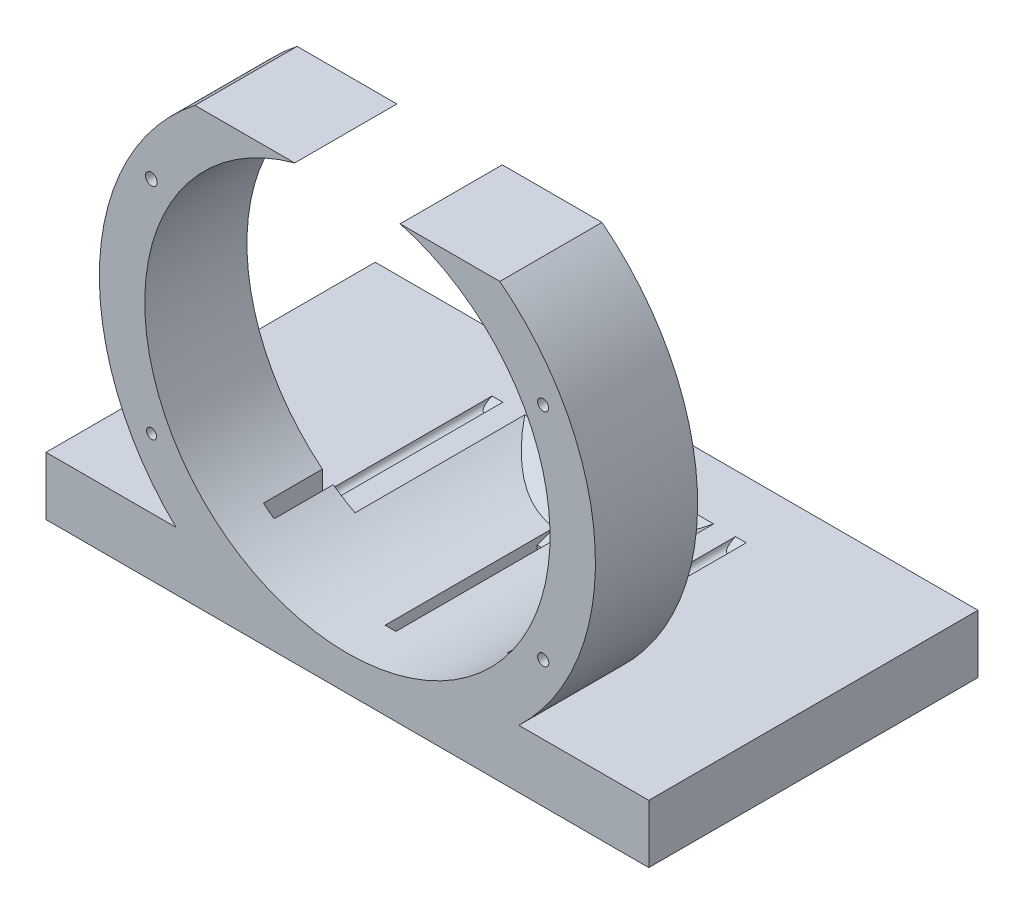
SolidWorks part; units mm, degrees
ref_plane "Front Plane" through (0, 0, 0) normal (0, 0, 1) x (1, 0, 0)
ref_plane "Top Plane" through (0, 0, 0) normal (0, 1, 0) x (1, 0, 0)
ref_plane "Right Plane" through (0, 0, 0) normal (1, 0, 0) x (0, 0, -1)
sketch "Sketch1" plane through (0, 0, 0) normal (0, 0, 1) x (1, 0, 0)
  line L0 (-34.1117, 43.7782) -> (34.1117, 43.7782)
  line L4 (28.448, -40.0843) -> (28.448, -35.2709)
  line L5 (-67.4363, -40.1112) -> (-38.3566, -40.1112)
  line L6 (-67.4363, -40.1112) -> (-67.4363, -53.1541)
  line L7 (-67.4363, -53.1541) -> (67.4363, -53.1541)
  line L8 (67.4363, -40.1112) -> (67.4363, -53.1541)
  line L9 (1.2065, -45.2975) -> (1.2065, -49.1871)
  line L10 (-1.2065, -45.2975) -> (-1.2065, -49.1871)
  line L12 (-28.448, -35.2709) -> (-28.448, -40.0843)
  line L13 (38.3566, -40.1112) -> (67.4363, -40.1112)
  line L14 (26.035, -37.0877) -> (26.035, -40.0843)
  line L16 (-26.035, -40.0843) -> (-26.035, -37.0877)
  arc A1 (-26.035, -37.1188) -> (-1.2065, -45.3229) centre (0, 0) ccw
  arc A2 (-34.1117, 43.7782) -> (-38.3566, -40.1112) centre (0, 0) ccw
  circle A3 centre (-43.8732, 24.6314) radius 1.3123
  arc A4 (38.3566, -40.1112) -> (34.1117, 43.7782) centre (0, 0) ccw
  circle A5 centre (-43.815, -24.6768) radius 1.1199
  circle A6 centre (43.815, -24.6768) radius 1.2511
  circle A7 centre (43.7914, 24.6952) radius 1.2263
  arc A9 (-1.2065, -49.1871) -> (1.2065, -49.1871) centre (0, -49.1871) ccw
  arc A10 (-28.448, -40.0843) -> (-26.035, -40.0843) centre (-27.2415, -40.0843) ccw
  arc A11 (1.2065, -45.3229) -> (26.035, -37.1188) centre (0, 0) ccw
  arc A12 (26.035, -40.0843) -> (28.448, -40.0843) centre (27.2415, -40.0843) ccw
  arc A13 (28.448, -35.3035) -> (-28.448, -35.3035) centre (0, 0) ccw
  point P8 (0, -45.339)
  dimension "D1" = 90.678
  dimension "D2" = 10.16
  dimension "D3" = 2.413
extrude "Boss-Extrude1" add sketch "Sketch1" along normal blind 22.86 contours L13 A4 L0 A1 A2 L5 L6 L7 L8 region at (-22.9528, 42.1173, 0)
sketch "Sketch2" plane through (0, 0, 0) normal (0, 0, -1) x (-1, 0, 0)
  line L0 (21.1356, -40.1112) -> (26.0353, -40.1112)
  line L1 (-67.4363, -53.1541) -> (67.4363, -53.1541)
  line L2 (-67.4363, -53.1541) -> (-67.4363, -40.1112)
  line L3 (-67.4363, -40.1112) -> (-28.4477, -40.1112)
  line L4 (67.4363, -53.1541) -> (67.4363, -40.1112)
  line L5 (1.2065, -49.1871) -> (1.2065, -45.3229)
  line L6 (28.4477, -40.1112) -> (67.4363, -40.1112)
  line L7 (-1.2065, -45.3229) -> (-1.2065, -49.1871)
  line L8 (-26.0353, -40.1112) -> (-21.1356, -40.1112)
  arc A0 (-21.1356, -40.1112) -> (-1.2065, -45.3229) centre (0, 0) ccw
  arc A1 (-28.4477, -40.1112) -> (-26.0353, -40.1112) centre (-27.2415, -40.0843) ccw
  arc A2 (-1.2065, -49.1871) -> (1.2065, -49.1871) centre (0, -49.1871) ccw
  arc A3 (26.0353, -40.1112) -> (28.4477, -40.1112) centre (27.2415, -40.0843) ccw
  arc A4 (1.2065, -45.3229) -> (21.1356, -40.1112) centre (0, 0) ccw
extrude "Boss-Extrude2" add sketch "Sketch2" along normal blind 50.8 contours L2 L3 A1 L8 A0 L7 A2 L5 A4 L0 A3 L6 L4 L1
sketch "Sketch3" plane through (0, 0, 0) normal (0, 0, -1) x (-1, 0, 0)
  line L0 (-28.448, 40.2554) -> (-28.448, 35.2709)
  line L1 (-28.448, 35.2709) -> (-26.035, 37.0877)
  line L2 (-26.035, 37.0877) -> (-26.035, 40.2554)
  line L3 (28.448, 40.2554) -> (28.448, 35.3035)
  line L4 (28.448, 35.3035) -> (26.0792, 37.0877)
  line L5 (26.0792, 37.0877) -> (26.035, 40.2554)
  arc A0 (-26.035, 40.2554) -> (-28.448, 40.2554) centre (-27.2415, 40.2554) ccw
  arc A1 (28.448, 40.2554) -> (26.0355, 40.2217) centre (27.2415, 40.2554) ccw
  arc A2 (28.448, -35.3035) -> (11.7939, 43.7782) centre (0, 0) ccw construction
  arc M5 (11.7939, 43.7782) -> (28.448, -35.3035) centre (0, 0) cw
extrude "Cut-Extrude1" cut sketch "Sketch3" against normal blind 13.208 contours L3 A1 L5 M5 | L2 A0 L0 L1 region at (27.3142, 38.671, 0) region at (-27.3223, 38.7004, 0)
sketch "Sketch4" plane through (0, 0, 22.86) normal (0, 0, 1) x (1, 0, 0)
  line L0 (-26.035, -40.0843) -> (-26.035, -37.1188)
  line L2 (-28.448, -35.3035) -> (-28.448, -40.0843)
  line L3 (-1.2065, -45.3229) -> (-1.2065, -49.1871)
  line L5 (1.2065, -45.2975) -> (1.2065, -49.1871)
  line L6 (28.448, -40.0843) -> (28.448, -35.3035)
  line L7 (1.1905, -45.3234) -> (1.2065, -45.2975)
  line L8 (26.035, -37.1188) -> (26.035, -40.0843)
  arc A0 (-28.448, -40.0843) -> (-26.035, -40.0843) centre (-27.2415, -40.0843) ccw
  arc A1 (-1.2065, -49.1871) -> (1.2065, -49.1871) centre (0, -49.1871) ccw
  arc A2 (26.035, -40.0843) -> (28.448, -40.0843) centre (27.2415, -40.0843) ccw
  arc A3 (-28.448, -35.3035) -> (-26.035, -37.1188) centre (0, 0) ccw
  arc A4 (-1.2065, -45.3229) -> (1.2065, -45.3229) centre (0, 0) ccw
  arc A5 (26.035, -37.1188) -> (28.448, -35.3035) centre (0, 0) ccw
  line M14 (28.448, -35.3035) -> (28.448, -40.0843)
  arc M15 (28.448, -40.0843) -> (26.035, -40.0843) centre (27.2415, -40.0843) cw
  line M16 (26.035, -40.0843) -> (26.035, -37.1188)
  line M18 (1.2065, -45.3229) -> (1.2065, -49.1871)
  arc M19 (1.2065, -49.1871) -> (-1.2065, -49.1871) centre (0, -49.1871) cw
  line M20 (-1.2065, -49.1871) -> (-1.2065, -45.3229)
  line M22 (-26.035, -37.1188) -> (-26.035, -40.0843)
  arc M23 (-26.035, -40.0843) -> (-28.448, -40.0843) centre (-27.2415, -40.0843) cw
  line M24 (-28.448, -40.0843) -> (-28.448, -35.3035)
extrude "Boss-Extrude3" add sketch "Sketch4" against normal blind 9.652 contours A3 M24 M23 M22 | A4 M20 M19 M18 | A5 M16 M15 M14 region at (-27.3175, -38.611, 22.86) region at (0, -47.7417, 22.86) region at (27.3175, -38.611, 22.86)
sketch "Sketch6" plane through (67.4363, 0, 0) normal (1, 0, 0) x (0, 0, -1)
  line L2 (20.8189, -46.8236) -> (20.8189, -53.1541)
  line L3 (50.8, -40.1112) -> (50.8, -45.3976)
  line L5 (-22.86, -53.1541) -> (50.8, -53.1541) construction
  line L6 (20.8189, -53.1541) -> (50.8, -53.1541)
  line L9 (50.8, -53.1541) -> (50.8, -45.3976)
  line L10 (50.8, -53.1541) -> (50.8, -40.1112) construction
  line L12 (50.8, -40.1112) -> (37.9477, -40.1112)
  line L13 (-22.86, -40.1112) -> (50.8, -40.1112) construction
  line L14 (37.9477, -40.1112) -> (20.8189, -46.8236)
  point P5 (19.7755, -40.1112)
  point P15 (16.719, -43.6118)
  point P16 (37.9477, -40.1112)
  point P17 (20.8189, -46.8236)
extrude "Boss-Extrude5" add sketch "Sketch6" against normal blind 116.84 contours L14 L2 L6 L9 L3 L12
